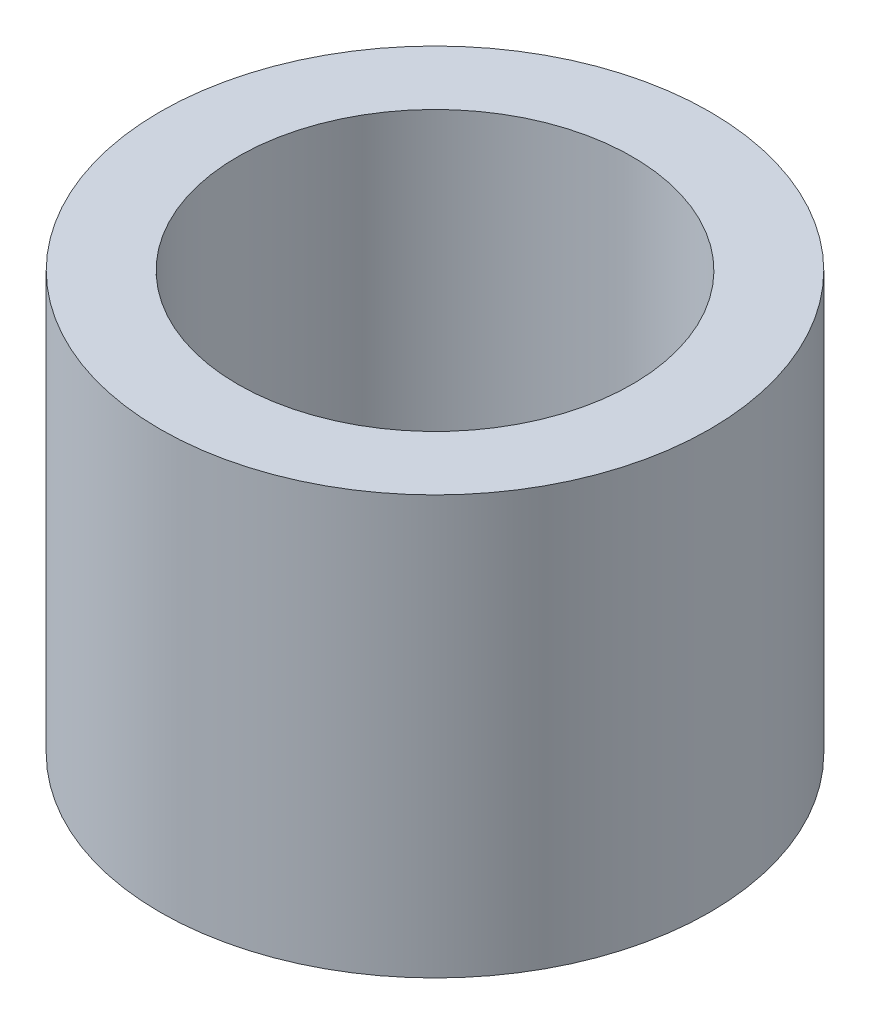
SolidWorks part; units mm, degrees
ref_plane "Спереди" through (0, 0, 0) normal (0, 0, 1) x (1, 0, 0)
ref_plane "Сверху" through (0, 0, 0) normal (0, 1, 0) x (1, 0, 0)
ref_plane "Справа" through (0, 0, 0) normal (1, 0, 0) x (0, 0, -1)
sketch "Эскиз1" plane through (0, 0, 0) normal (0, 1, 0) x (1, 0, 0)
  circle A0 centre (0, 0) radius 23
  dimension "D1" = 46
extrude "Бобышка-Вытянуть1" add sketch "Эскиз1" along normal blind 5
sketch "Эскиз2" plane through (0, 5, 0) normal (0, 1, 0) x (1, 0, 0)
  circle A0 centre (0, 0) radius 23
  circle A1 centre (0, 0) radius 16.5
  circle A2 centre (0, 0) radius 23 construction
  dimension "D1" = 33
  dimension "D2" = 0
extrude "Бобышка-Вытянуть2" add sketch "Эскиз2" along normal blind 30
